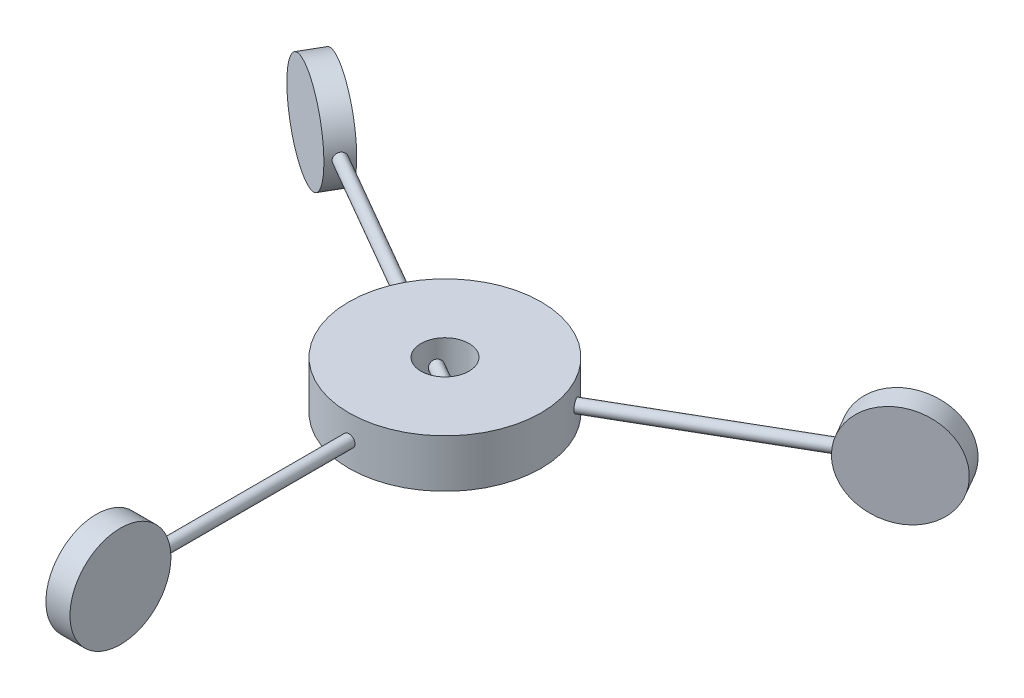
SolidWorks part; units mm, degrees
material "Custom Plastic"
ref_plane "Front Plane" through (0, 0, 0) normal (0, 0, 1) x (1, 0, 0)
ref_plane "Top Plane" through (0, 0, 0) normal (0, 1, 0) x (1, 0, 0)
ref_plane "Right Plane" through (0, 0, 0) normal (1, 0, 0) x (0, 0, -1)
sketch "Sketch1" plane through (0, 0, 0) normal (0, 1, 0) x (1, 0, 0)
  circle A0 centre (0, 0) radius 25.4
  circle A1 centre (0, 0) radius 6.35
  dimension "D1" = 50.8
  dimension "D2" = 12.7
extrude "Boss-Extrude1" add sketch "Sketch1" along normal blind 12.7
sketch "Sketch2" plane through (0, 0, 0) normal (0, 0, 1) x (1, 0, 0)
  circle A0 centre (0, 6.35) radius 1.5875
  dimension "D2" = 3.175
  dimension "D1" = 6.35
extrude "Boss-Extrude2" add sketch "Sketch2" along normal blind 76.2
ref_axis "Axis1" through (0, 12.7, 0) along (0, -1, 0)
pattern_circular "CirPattern1" count 3 over 360 about axis through (0, 12.7, 0) along (0, -1, 0) of "Boss-Extrude2"
sketch "Sketch3" plane through (0, 0, 0) normal (1, 0, 0) x (0, 0, -1)
  line L0 (-76.2, 7.9375) -> (-76.2, 4.7625) construction
  circle A0 centre (-88.9, 6.35) radius 13.335
  dimension "D1" = 26.67
  dimension "D2" = 12.7
  dimension "D3" = 6.35
extrude "Boss-Extrude3" add sketch "Sketch3" along normal blind 3.175 and the other way blind 3.175 separate body
pattern_circular "CirPattern10" count 3 over 360 about axis through (0, 12.7, 0) along (0, -1, 0) of bodies 104
